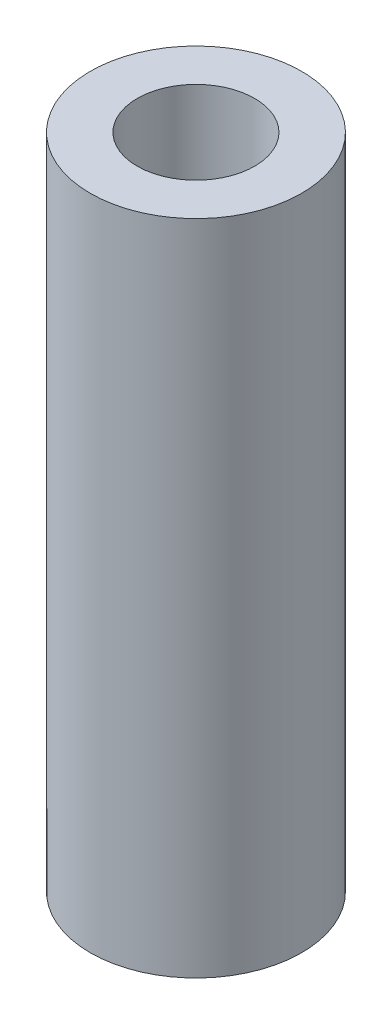
SolidWorks part; units mm, degrees
material "Natural Rubber"
ref_plane "Front Plane" through (0, 0, 0) normal (0, 0, 1) x (1, 0, 0)
ref_plane "Top Plane" through (0, 0, 0) normal (0, 1, 0) x (1, 0, 0)
ref_plane "Right Plane" through (0, 0, 0) normal (1, 0, 0) x (0, 0, -1)
sketch "Sketch2" plane through (0, 0, 0) normal (0, 1, 0) x (1, 0, 0)
  circle A0 centre (0, 0) radius 57.15
  circle A1 centre (0, 0) radius 31.75
extrude "Boss-Extrude1" add sketch "Sketch2" along normal blind 355.6
